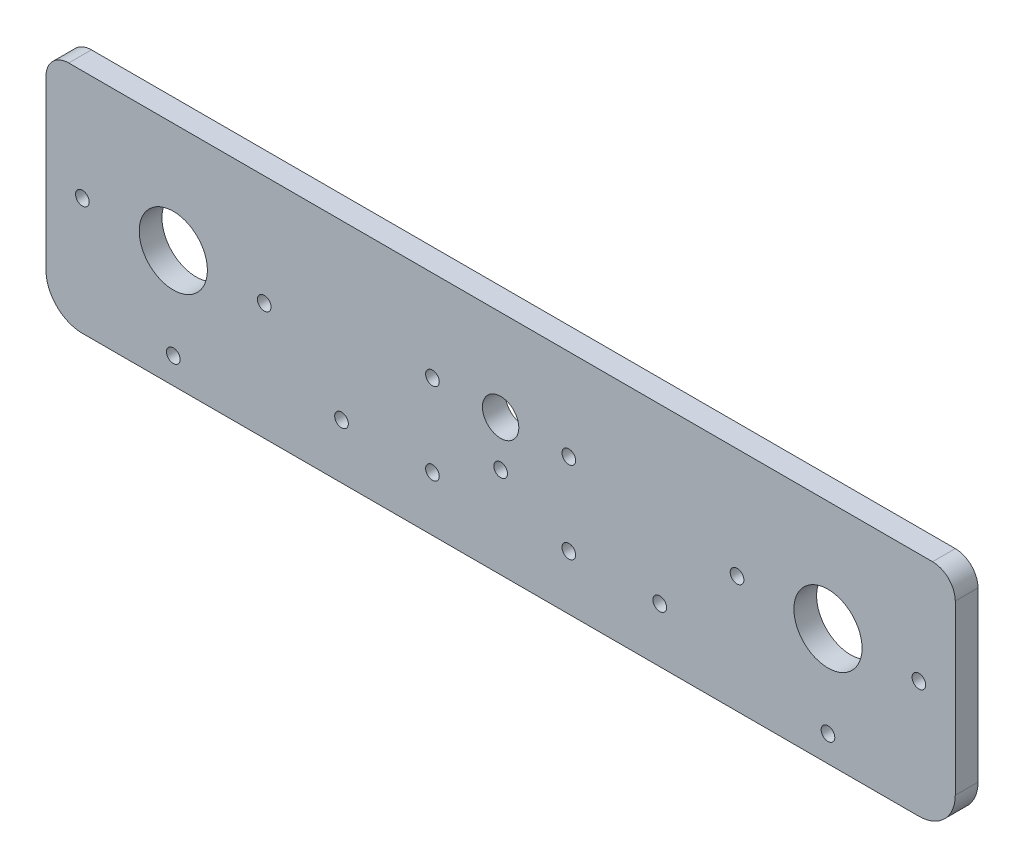
SolidWorks part; units mm, degrees
ref_plane "Alzado" through (0, 0, 0) normal (0, 0, 1) x (1, 0, 0)
ref_plane "Planta" through (0, 0, 0) normal (0, 1, 0) x (1, 0, 0)
ref_plane "Vista lateral" through (0, 0, 0) normal (1, 0, 0) x (0, 0, -1)
sketch "Croquis1" plane through (0, 0, 0) normal (0, 0, 1) x (1, 0, 0)
  line L0 (0, 0) -> (100, 0) construction
  line L1 (0, 0) -> (0, -15) construction
  line L2 (72, 0) -> (72, -19.25) construction
  line L3 (100, 0) -> (100, -37)
  line L4 (92, -45) -> (-92, -45)
  line L5 (0, -45) -> (0, -15) construction
  line L6 (0, 0) -> (0, 5) construction
  line L7 (-100, 5) -> (100, 5)
  line L8 (100, 5) -> (100, 0)
  line L9 (-100, 5) -> (-100, 0)
  line L10 (-100, 0) -> (-100, -37)
  circle A0 centre (0, -15) radius 4
  circle A1 centre (72, -19.25) radius 7.5
  circle A2 centre (-72, -19.25) radius 7.5
  circle A3 centre (72, -39.25) radius 1.5
  circle A4 centre (52, -19.25) radius 1.5
  circle A5 centre (92, -19.25) radius 1.5
  circle A6 centre (-72, -19.25) radius 7.5
  circle A7 centre (-72, -39.25) radius 1.5
  circle A8 centre (-92, -19.25) radius 1.5
  circle A9 centre (-52, -19.25) radius 1.5
  arc A10 (100, -37) -> (92, -45) centre (92, -37) cw
  arc A11 (-100, -37) -> (-92, -45) centre (-92, -37) ccw
  circle A12 centre (15, -33) radius 1.5
  circle A13 centre (35, -33) radius 1.5
  circle A14 centre (-35, -33) radius 1.5
  circle A15 centre (-15, -33) radius 1.5
  circle A16 centre (-15, -15) radius 1.5
  circle A17 centre (15, -15) radius 1.5
  circle A18 centre (0, -25) radius 1.5
  point P34 (100, -45)
  point P37 (-100, -45)
  dimension "D4" = 8
  dimension "D5" = 15
  dimension "D10" = 3
  dimension "D11" = 3
  dimension "D13" = 8
  dimension "D14" = 3
  dimension "D15" = 3
  dimension "D19" = 3
  dimension "D21" = 3
  dimension "D1" = 19.25
  dimension "D2" = 15
  dimension "D3" = 72
  dimension "D6" = 100
  dimension "D7" = 45
  dimension "D8" = 20
  dimension "D9" = 20
  dimension "D12" = 5
  dimension "D16" = 20
  dimension "D17" = 15
  dimension "D18" = 12
  dimension "D20" = 15
  dimension "D22" = 10
extrude "Saliente-Extruir1" add sketch "Croquis1" along normal blind 5 contours L9 L10 L4 L3 L8 L7 A7 A2 A1 A0 A3 A4 A5 A8 A9 region at (0, -19.9257, 0)
fillet "Redondeo1" radius 5 2 edges at (100, 5, 2.5) (-100, 5, 2.5)
